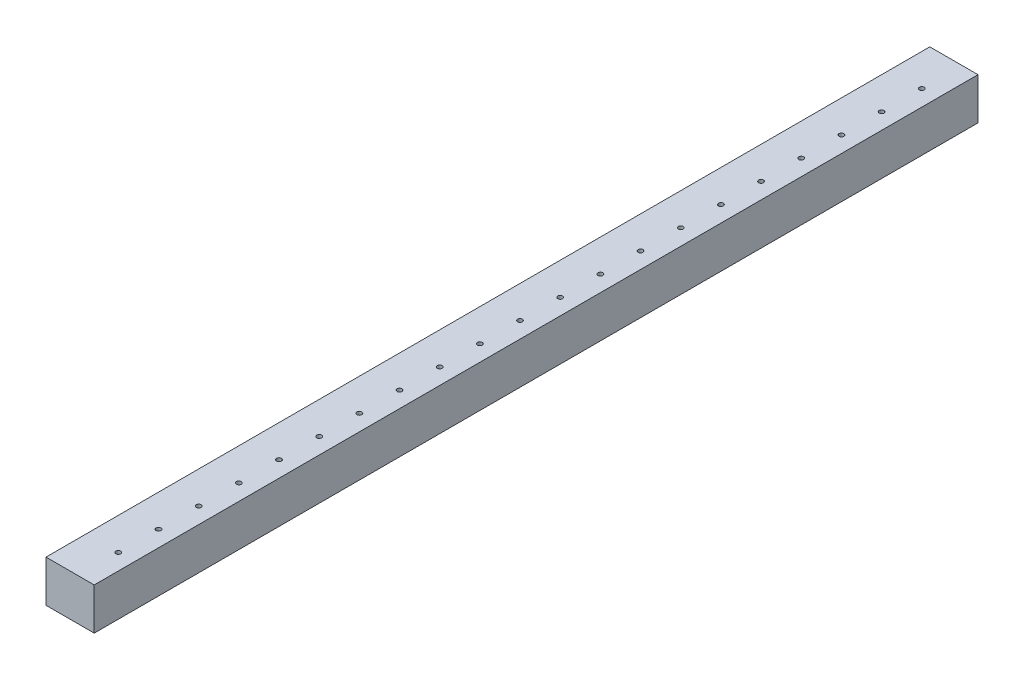
SolidWorks part; units mm, degrees
ref_plane "Plan de face" through (0, 0, 0) normal (0, 0, 1) x (1, 0, 0)
ref_plane "Plan de dessus" through (0, 0, 0) normal (0, 1, 0) x (1, 0, 0)
ref_plane "Plan de droite" through (0, 0, 0) normal (1, 0, 0) x (0, 0, -1)
sketch "Esquisse1" plane through (0, 0, 0) normal (0, 0, 1) x (1, 0, 0)
  line L1 (-15, 18) -> (15, 18)
  line L2 (-15, 18) -> (-15, -18)
  line L3 (-15, -18) -> (15, -18)
  line L4 (15, 18) -> (15, -18)
  line L5 (-15, 18) -> (15, -18) construction
  line L6 (-15, -18) -> (15, 18) construction
  point P0 (0, 0)
  dimension "D1" = 36
  dimension "D2" = 30
extrude "Boss.-Extru.1" add sketch "Esquisse1" along normal blind 550
sketch "Esquisse2" plane through (0, 0, 550) normal (0, 0, 1) x (1, 0, 0)
  line L1 (15, 18) -> (-5, 18)
  line L2 (15, 18) -> (15, 8)
  line L3 (15, 8) -> (-5, 8)
  line L4 (-5, 18) -> (-5, 8)
  dimension "D1" = 10
  dimension "D2" = 20
extrude "Enlèv. mat.-Extru.1" cut sketch "Esquisse2" against normal through all both and the other way through all
sketch "Esquisse3" plane through (0, 8, 0) normal (0, 1, 0) x (1, 0, 0)
  line L0 (-5, -550) -> (15, -550) construction
  line L1 (15, 0) -> (15, -550) construction
  circle A0 centre (5, -275) radius 1.5
  point P2 (0, 0)
  point P5 (5, -550)
  point P8 (15, -275)
  dimension "D1" = 3
extrude "Enlèv. mat.-Extru.2" cut sketch "Esquisse3" against normal blind 20
pattern_linear "Répétition linéaire1" count 11 spacing 25 along (0, 0, -1) count 11 spacing 25 along (0, 0, 1) of "Enlèv. mat.-Extru.2"
sketch "Esquisse4" plane through (0, 0, 550) normal (0, 0, 1) x (1, 0, 0)
  line L1 (-5, 8) -> (-15, 8)
  line L2 (-5, 8) -> (-5, 18)
  line L3 (-5, 18) -> (-15, 18)
  line L4 (-15, 8) -> (-15, 18)
extrude "Enlèv. mat.-Extru.3" cut sketch "Esquisse4" against normal through all both and the other way through all
